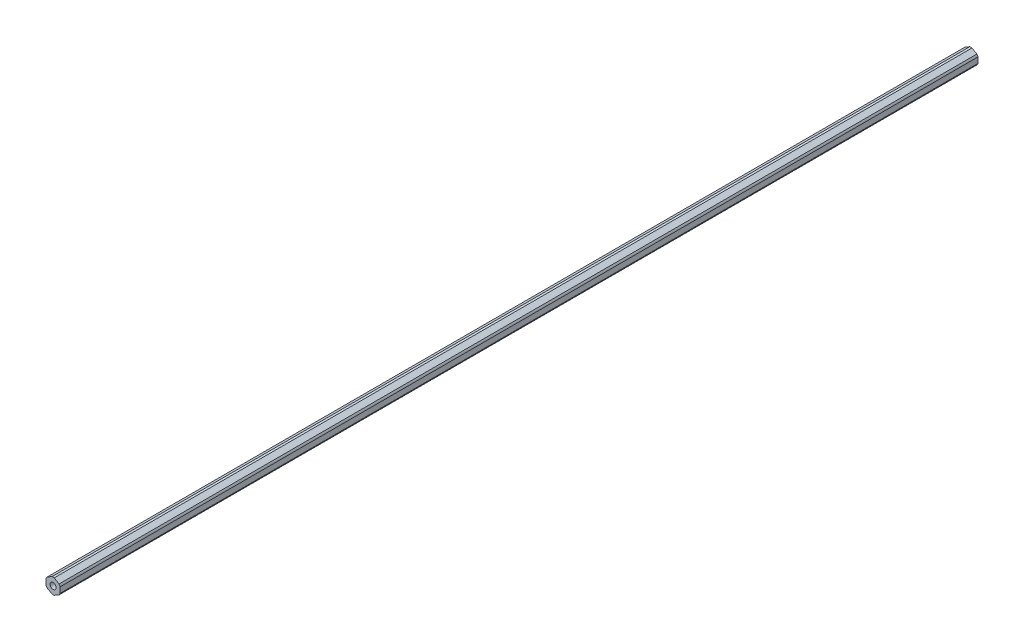
SolidWorks part; units mm, degrees
material "7075-T6 (SN)"
ref_plane "Front Plane" through (0, 0, 0) normal (0, 0, 1) x (1, 0, 0)
ref_plane "Top Plane" through (0, 0, 0) normal (0, 1, 0) x (1, 0, 0)
ref_plane "Right Plane" through (0, 0, 0) normal (1, 0, 0) x (0, 0, -1)
sketch "Sketch2" plane through (0, 0, 0) normal (0, 0, 1) x (1, 0, 0)
  line L1 (0, 5.4993) -> (-4.7625, 2.7496)
  line L2 (-4.7625, 2.7496) -> (-4.7625, -2.7496)
  line L3 (-4.7625, -2.7496) -> (0, -5.4993)
  line L4 (0, -5.4993) -> (4.7625, -2.7496)
  line L5 (4.7625, -2.7496) -> (4.7625, 2.7496)
  line L6 (4.7625, 2.7496) -> (0, 5.4993)
  circle A0 centre (0, 0) radius 4.7625 construction
  circle A2 centre (0, 0) radius 2.0193
  circle A3 centre (0, 0) radius 5.125
  dimension "D1" = 9.525
  dimension "D2" = 10.25
  dimension "D3" = 4.0386
extrude "Boss-Extrude1" add sketch "Sketch2" along normal mid plane 615.744 contours L5 A3 L6 L1 L2 L3 L4 A2 region at (0, 4.9851, 0)
hole_wizard "#10-32 Tapped Hole2" positions "3DSketch1" profile "Sketch6" tap size "#10-32" standard "ANSI Inch"
sketch3d "3DSketch1"
  circle A0 centre (0, 0, 307.872) radius 2.0193 construction
  circle A1 centre (0, 0, -307.872) radius 2.0193 construction
  point P0 (0, 0, -307.872)
  point P2 (0, 0, 307.872)
  point P7 (0, 0, 309.8913)
  point P10 (0, 0, -305.8527)
sketch "Sketch6" plane through (0, 0, -307.872) normal (1, 0, 0) x (0, 1, 0)
  line L0 (0, 0) -> (0, 17.5608)
  line L1 (0, 17.5608) -> (2.0193, 16.3474)
  line L2 (2.0193, 16.3474) -> (2.0193, 0)
  line L5 (2.0193, 0) -> (0, 0)
  line L10 (0, 17.5608) -> (-2.0193, 16.3474) construction
  line L11 (0, -6.35) -> (0, 107.95) construction
  dimension "Tap Drill Dia." = 4.0386
  dimension "Tap Drill Depth" = 16.3474
  dimension "Drill Angle" = 118
cosmetic thread "Hole Thread2" parameters "D1"=13.97, "D2"=4.826
cosmetic thread "Hole Thread3" parameters "D1"=13.97, "D2"=4.826
equation "\"D2@Sketch2\"=10.25mm"
